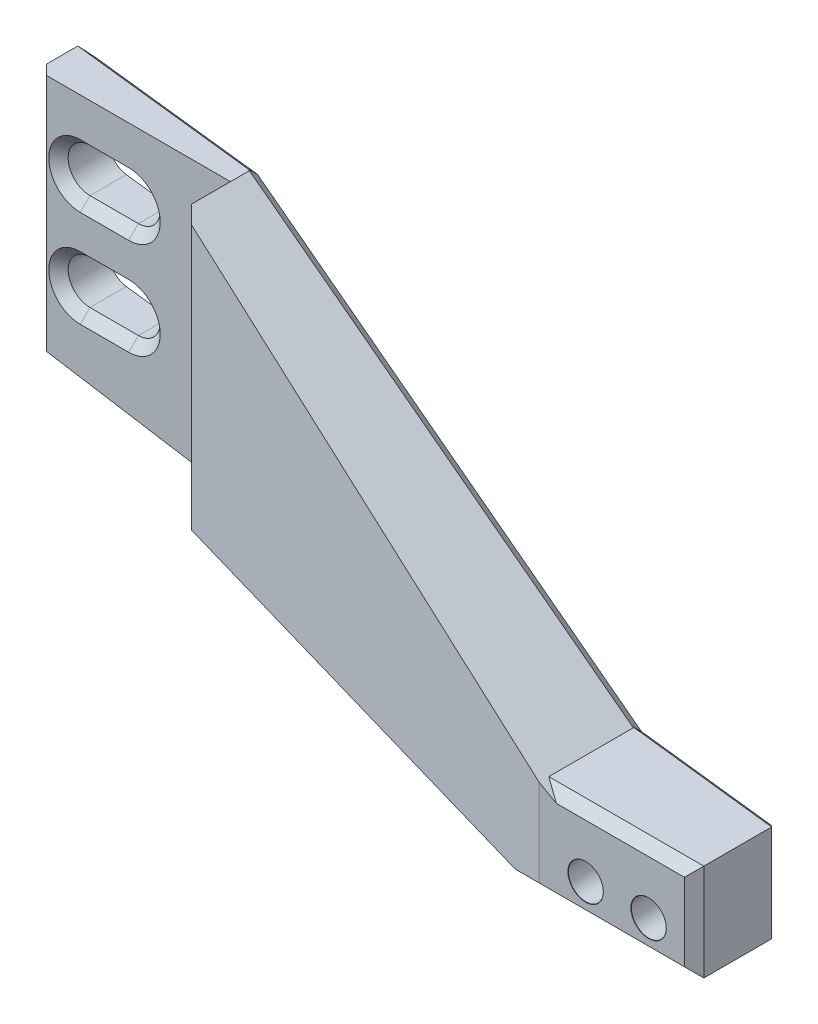
SolidWorks part; units mm, degrees
ref_plane "Front Plane" through (0, 0, 0) normal (0, 0, 1) x (1, 0, 0)
ref_plane "Top Plane" through (0, 0, 0) normal (0, 1, 0) x (1, 0, 0)
ref_plane "Right Plane" through (0, 0, 0) normal (1, 0, 0) x (0, 0, -1)
sketch "Sketch1" plane through (0, 0, 0) normal (0, 0, 1) x (1, 0, 0)
  line L0 (0, 0) -> (0, 24.5)
  line L1 (0, 24.5) -> (64.6, 35)
  line L2 (64.6, 35) -> (80.6, 35)
  line L3 (80.6, 35) -> (80.6, 25)
  line L4 (80.6, 25) -> (64.6, 25)
  line L5 (64.6, 25) -> (20, 0)
  line L6 (20, 0) -> (0, 0)
  line L7 (4.5, 17.25) -> (9.5, 17.25) construction
  line L8 (4.5, 19.5) -> (9.5, 19.5)
  line L9 (4.5, 15) -> (9.5, 15)
  line L10 (4.5, 7.25) -> (9.5, 7.25) construction
  line L11 (4.5, 9.5) -> (9.5, 9.5)
  line L12 (4.5, 5) -> (9.5, 5)
  line L13 (7, 17.25) -> (7, 7.25) construction
  line L14 (64.6, 35) -> (64.6, 25) construction
  arc A0 (4.5, 19.5) -> (4.5, 15) centre (4.5, 17.25) ccw
  arc A1 (9.5, 15) -> (9.5, 19.5) centre (9.5, 17.25) ccw
  arc A2 (4.5, 9.5) -> (4.5, 5) centre (4.5, 7.25) ccw
  arc A3 (9.5, 5) -> (9.5, 9.5) centre (9.5, 7.25) ccw
  point P10 (7, 17.25)
  point P16 (7, 7.25)
  dimension "D4" = 2.25
  dimension "D1" = 10
  dimension "D2" = 16
  dimension "D3" = 5
  dimension "D5" = 5
  dimension "D6" = 5.5
  dimension "D7" = 5
  dimension "D8" = 80.6
  dimension "D9" = 10.5
  dimension "D10" = 20
  dimension "D11" = 4.5
extrude "Boss-Extrude1" add sketch "Sketch1" along normal blind 18 contours L5 L6 L0 L1 L2 L3 L4
sketch "Sketch2" plane through (0, 0, 0) normal (0, -1, 0) x (1, 0, 0)
  line L0 (0, 5.2519) -> (20, 5.2519)
  line L2 (20, 5.2519) -> (20, 10.2519)
  line L3 (20, 10.2519) -> (64.6, 18)
  line L5 (64.6, 18) -> (0, 18)
  line L6 (0, 18) -> (0, 5.2519)
  line L7 (0, 0) -> (80.6, 9)
  line L10 (80.6, 9) -> (80.6, 0)
  line L11 (80.6, 0) -> (0, 0)
  line L12 (20, 18) -> (20, 0) construction
  line L13 (80.6, 18) -> (80.6, 0) construction
  line L14 (0, 18) -> (0, 0) construction
  dimension "D1" = 3
  dimension "D2" = 5
extrude "Cut-Extrude1" cut sketch "Sketch2" against normal through all
chamfer "Chamfer1" distance 1 angle 45 20 edges at (0, 12.25, 0) (0, 12.25, 5.2519) (72.6, 35, 8.1067) (80.6, 30, 9) (72.6, 25, 8.1067) (42.3, 12.5, 4.7233) (10, 0, 1.1166) (32.3, 29.75, 3.6067) (72.6, 25, 18) (80.6, 30, 18) (72.6, 35, 18) (20, 13.8754, 10.2519) (7, 5, 5.2519) (2.25, 7.25, 5.2519) (11.75, 7.25, 5.2519) (7, 9.5, 5.2519) (7, 15, 5.2519) (2.25, 17.25, 5.2519) (11.75, 17.25, 5.2519) (7, 19.5, 5.2519)
hole_wizard "M3 Clearance Hole1" positions "Sketch3" profile "Sketch6" hole size "M3" standard "ISO"
sketch "Sketch3" plane through (0, 0, 18) normal (0, 0, 1) x (1, 0, 0)
  line L0 (69.4, 31.5) -> (75.9, 31.5)
  line L1 (75.9, 31.5) -> (80.6, 31.5)
  line L2 (80.6, 35) -> (80.6, 25) construction
  line L5 (74.1531, 31.5) -> (74.1531, 35)
  line L6 (64.6, 35) -> (80.6, 35) construction
  point P1 (69.4, 31.5)
  point P2 (75.9, 31.5)
  dimension "D1" = 4.7
  dimension "D2" = 3.5
  dimension "D3" = 6.5
sketch "Sketch6" plane through (69.4, 31.5, 18) normal (1, 0, 0) x (0, -1, 0)
  line L0 (0, 0) -> (0, 5.5)
  line L1 (0, 5.5) -> (1.8, 4.4185)
  line L2 (1.8, 4.4185) -> (1.8, 0.025)
  line L3 (1.8, 0.025) -> (1.825, 0)
  line L5 (1.825, 0) -> (0, 0)
  line L6 (-1.8, 0.025) -> (-1.825, 0) construction
  line L10 (0, 5.5) -> (-1.8, 4.4185) construction
  line L11 (0, -6.35) -> (0, 107.95) construction
  dimension "Hole Dia." = 3.6
  dimension "Hole Depth" = 5.5
  dimension "Near C'Sink Dia." = 3.65
  dimension "Near C'Sink Angle" = 90
  dimension "Drill Angle" = 118
mirror "Mirror2" about plane through (20, 0, 18) normal (0, 1, 0) of bodies 103
delete or keep bodies "Body-Delete/Keep 1" type delete bodies bodies 103
